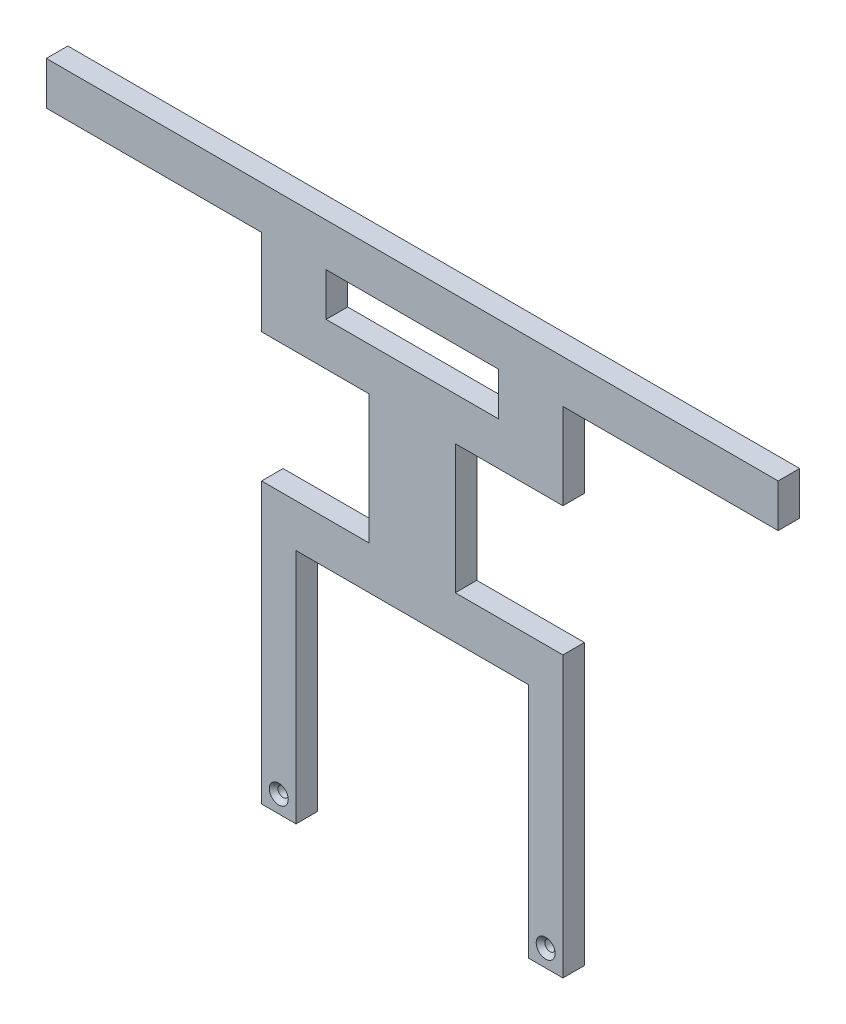
SolidWorks part; units mm, degrees
ref_plane "Plan de face" through (0, 0, 0) normal (0, 0, 1) x (1, 0, 0)
ref_plane "Plan de dessus" through (0, 0, 0) normal (0, 1, 0) x (1, 0, 0)
ref_plane "Plan de droite" through (0, 0, 0) normal (1, 0, 0) x (0, 0, -1)
sketch "Esquisse1" plane through (0, 0, 0) normal (0, 0, 1) x (1, 0, 0)
  line L20 (0, 0) -> (0, 65)
  line L21 (0, 65) -> (25, 65)
  line L22 (25, 65) -> (25, 95)
  line L23 (25, 95) -> (0, 95)
  line L24 (0, 95) -> (0, 115)
  line L25 (0, 115) -> (-50, 115)
  line L26 (-50, 115) -> (-50, 125)
  line L27 (-50, 125) -> (35, 125)
  line L28 (35, 125) -> (35, 115)
  line L29 (35, 115) -> (15, 115)
  line L30 (15, 115) -> (15, 105)
  line L31 (15, 105) -> (35, 105)
  line L32 (35, 105) -> (35, 55)
  line L33 (35, 55) -> (8, 55)
  line L34 (8, 55) -> (8, 0)
  line L35 (8, 0) -> (0, 0)
  dimension "D1" = 65
  dimension "D2" = 8
  dimension "D3" = 55
  dimension "D4" = 25
  dimension "D5" = 30
  dimension "D6" = 20
  dimension "D7" = 50
  dimension "D8" = 10
  dimension "D9" = 27
  dimension "D10" = 10
  dimension "20" = 20
  dimension "D11" = 20
  dimension "D12" = 50
extrude "Boss.-Extru.1" add sketch "Esquisse1" along normal blind 5
mirror "Symétrie1" about plane through (35, 105, 5) normal (-1, 0, 0) of "Boss.-Extru.1"
sketch "Esquisse2" plane through (0, 0, 5) normal (0, 0, 1) x (1, 0, 0)
  line L0 (8, 0) -> (8, 55) construction
  line L1 (0, 0) -> (8, 0) construction
  line L2 (70, 65) -> (70, 0) construction
  line L3 (70, 0) -> (62, 0) construction
  circle A0 centre (4, 4) radius 1
  circle A1 centre (66, 4) radius 1
  dimension "D3" = 2
  dimension "D6" = 2
  dimension "D1" = 4
  dimension "D2" = 4
  dimension "D4" = 4
  dimension "D5" = 4
hole_wizard "Fraisage pour vis à tête fraisée M21" positions "Esquisse3" profile "Esquisse5" countersink size "M2" standard "ISO" end condition through all
sketch "Esquisse3" plane through (0, 0, 5) normal (0, 0, 1) x (1, 0, 0)
  point P0 (4, 4)
  point P3 (66, 4)
sketch "Esquisse5" plane through (4, 4, 5) normal (1, 0, 0) x (0, -1, 0)
  line L0 (0, 0) -> (0, 5)
  line L1 (0, 5) -> (1.2, 5)
  line L2 (1.2, 5) -> (1.2, 1)
  line L3 (1.2, 1) -> (2.2, 0)
  line L5 (2.2, 0) -> (0, 0)
  line L6 (-1.2, 1) -> (-2.2, 0) construction
  line L11 (0, -6.35) -> (0, 107.95) construction
  dimension "Diamètre du perçage jusqu'au prochain" = 2.4
  dimension "Profondeur du perçage jusqu'au prochain" = 5
  dimension "Diamètre du fraisage entrant" = 4.4
  dimension "Angle du fraisage entrant" = 90
